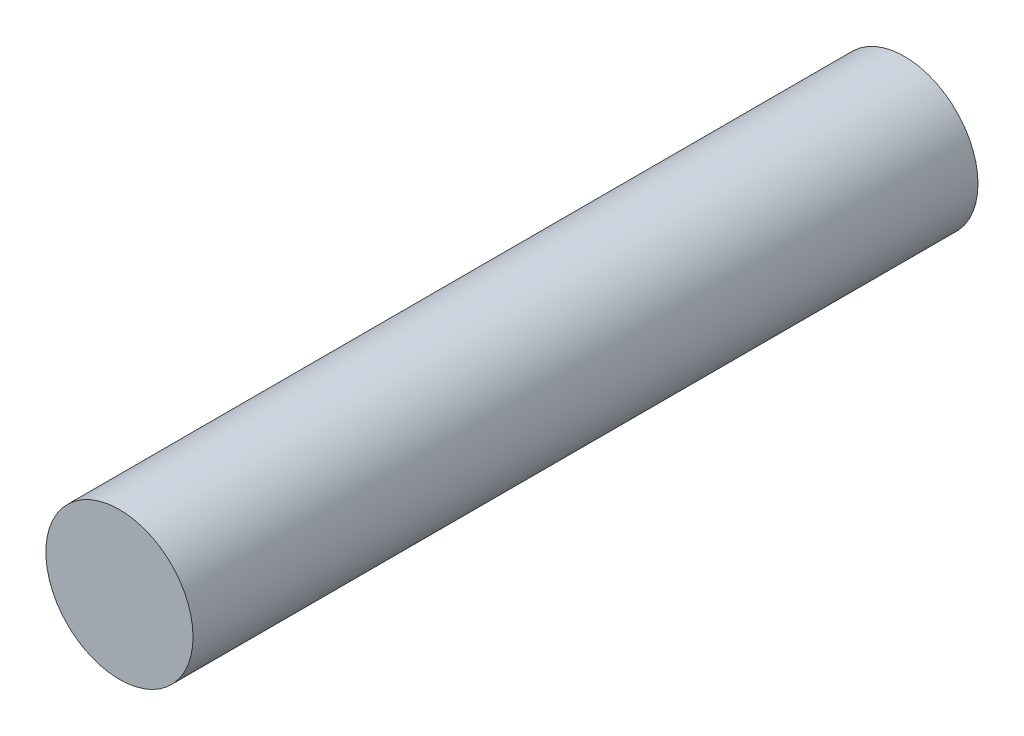
SolidWorks part; units mm, degrees
ref_plane "Front Plane" through (0, 0, 0) normal (0, 0, 1) x (1, 0, 0)
ref_plane "Top Plane" through (0, 0, 0) normal (0, 1, 0) x (1, 0, 0)
ref_plane "Right Plane" through (0, 0, 0) normal (1, 0, 0) x (0, 0, -1)
sketch "Sketch1" plane through (0, 0, 0) normal (0, 0, 1) x (1, 0, 0)
  circle A0 centre (0, 0) radius 37.5
  dimension "D1" = 75
extrude "Boss-Extrude1" add sketch "Sketch1" along normal blind 400
